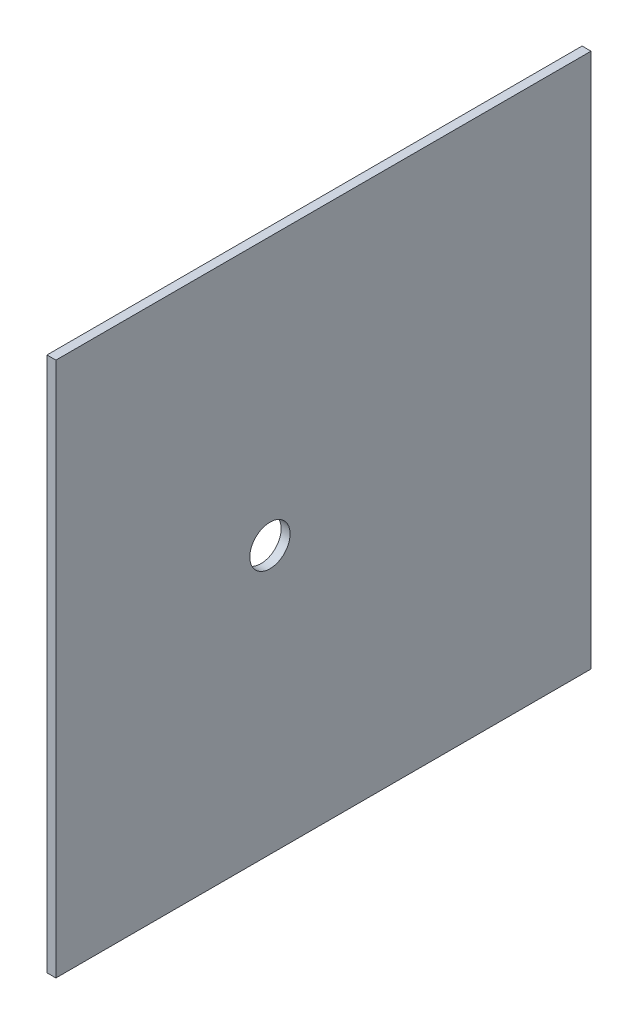
SolidWorks part; units mm, degrees
ref_plane "Front Plane" through (0, 0, 0) normal (0, 0, 1) x (1, 0, 0)
ref_plane "Top Plane" through (0, 0, 0) normal (0, 1, 0) x (1, 0, 0)
ref_plane "Right Plane" through (0, 0, 0) normal (1, 0, 0) x (0, 0, -1)
sketch "Sketch1" plane through (0, 0, 0) normal (1, 0, 0) x (0, 0, -1)
  line L1 (190.5, 190.5) -> (-190.5, 190.5)
  line L2 (190.5, 190.5) -> (190.5, -190.5)
  line L3 (190.5, -190.5) -> (-190.5, -190.5)
  line L4 (-190.5, 190.5) -> (-190.5, -190.5)
  line L5 (190.5, 190.5) -> (-190.5, -190.5) construction
  line L6 (190.5, -190.5) -> (-190.5, 190.5) construction
  circle A0 centre (-38.1, 0) radius 14.351
  point P0 (0, 0)
  dimension "D3" = 28.702
  dimension "D4" = 228.6
  dimension "D1" = 381
  dimension "D2" = 381
  dimension "D5" = 190.5
extrude "Boss-Extrude1" add sketch "Sketch1" along normal blind 6.35
